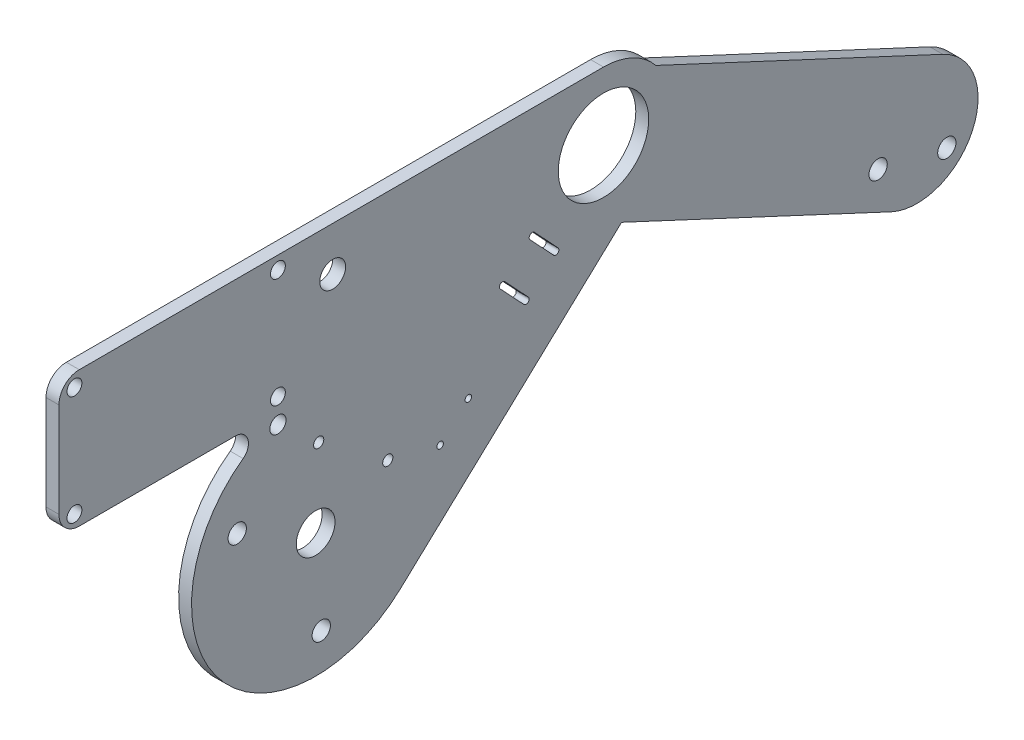
SolidWorks part; units mm, degrees
material "6061 Alloy"
ref_plane "Front Plane" through (0, 0, 0) normal (0, 0, 1) x (1, 0, 0)
ref_plane "Top Plane" through (0, 0, 0) normal (0, 1, 0) x (1, 0, 0)
ref_plane "Right Plane" through (0, 0, 0) normal (1, 0, 0) x (0, 0, -1)
sketch "Sketch1" plane through (0, 0, 0) normal (1, 0, 0) x (0, 0, -1)
  line L0 (-49.9001, -69.4268) -> (11.3662, -12.16)
  line L1 (-133.81, 16.645) -> (-76.19, 16.645)
  line L2 (-133.81, 16.645) -> (-133.81, -16.645)
  line L3 (-133.81, -16.645) -> (-76.19, -16.645)
  line L4 (-76.19, 16.645) -> (-76.19, -16.645)
  line L5 (-130, 13.475) -> (-80, 13.475)
  line L6 (-130, 13.475) -> (-130, -13.475)
  line L7 (-130, -13.475) -> (-80, -13.475)
  line L8 (-80, 13.475) -> (-80, -13.475)
  line L9 (-76.19, 16.645) -> (0, 16.645)
  line L10 (-83.2811, -19.3484) -> (-6.8511, 15.1697)
  line L11 (-130, -13.475) -> (-130, -19.435)
  line L12 (-80, -13.475) -> (-80, -19.435)
  line L13 (-76.19, -16.645) -> (0, -16.645)
  circle A0 centre (0, 0) radius 11.1125
  circle A1 centre (-70.7273, -47.145) radius 4.7625
  circle A2 centre (-70.7273, -47.145) radius 23.015 construction
  circle A3 centre (-70.7273, -47.145) radius 30.5
  circle A4 centre (0, 0) radius 16.645
  circle A5 centre (-130, -19.435) radius 2
  circle A6 centre (-80, -19.435) radius 2
  point P4 (-133.81, 0)
  point P12 (-130, 0)
  dimension "D6" = 22.225
  dimension "D7" = 9.525
  dimension "D8" = 46.03
  dimension "D9" = 61
  dimension "D11" = 0
  dimension "D14" = 4
  dimension "D1" = 33.29
  dimension "D2" = 80
  dimension "D3" = 26.95
  dimension "D4" = 50
  dimension "D5" = 3.81
  dimension "D10" = 85
  dimension "D12" = 3.81
  dimension "D13" = 5.96
extrude "Boss-Extrude1" add sketch "Sketch1" along normal mid plane 3.175 contours A6 A3 A1 | A4 L13 A3 L0 | A4 A0 | A4 L10 L4 L13 | A4 L9 L4 L10 | L8 L12 L3 L10 L4 L1 L2 L11 L6 L5 | L8 L5 L6 L7 | L12 L7 L11 L3 | A6 A3 L13 L3 L10 | L10 L3 L4 | A3 A6 | A3 A6 L10 L12 | L10 A6 A3 L12 | A6 L10 A3 region at (0, -30.4378, 28.398) region at (0, -63.5833, 95.3881) region at (0, -15.0453, -5.9367) region at (0, -18.8843, 82.226) region at (0, -7.4928, 34.7947) region at (0, -18.2558, 80.7031) region at (0, -19.6484, 79.9286) region at (0, -17.0177, 76.5839) region at (0, 5.7227, 51.9516) region at (0, -17.8085, 79.5096) region at (0, -16.4786, 76.5584) region at (0, -15.7889, 77.0165) region at (0, -15.06, 105) region at (0, 0, 105)
sketch "Sketch12" plane through (0, 0, 0) normal (1, 0, 0) x (0, 0, -1)
  line L0 (0, 0) -> (77.0362, -35.9226) construction
  line L1 (6.3393, 13.5946) -> (83.3754, -22.3279)
  line L2 (-6.3393, -13.5946) -> (70.6969, -49.5172)
  line L3 (-1000, 0) -> (49000, 0) construction
  line L5 (-4.9661, -14.2349) -> (77.7852, -34.0471) construction
  arc A0 (6.3393, 13.5946) -> (-6.3393, -13.5946) centre (0, 0) ccw
  arc A1 (70.6969, -49.5172) -> (83.3754, -22.3279) centre (77.0362, -35.9226) ccw
  circle A2 centre (0, 0) radius 11.1125 construction
  circle A3 centre (0, 0) radius 11.1125
  arc A5 (77.7852, -34.0471) -> (91.9205, -34.0633) centre (84.8868, -4.3854) ccw construction
  point P3 (38.5181, -17.9613)
  dimension "D1" = 85
  dimension "D2" = 30
  dimension "D3" = 25
extrude "Boss-Extrude2" add sketch "Sketch12" along normal mid plane 3.175 contours L2 A1 L1 A0 region at (0, -20.3901, -43.7267)
hole_wizard "#6 Clearance Hole1" positions "Sketch2" profile "Sketch3" hole size "#6" standard "ANSI Inch" end condition up to next
sketch "Sketch2" plane through (1.5875, 0, 0) normal (1, 0, 0) x (0, 0, -1)
  point P0 (-80, -13.475)
  point P3 (-80, 13.475)
  point P6 (-130, 13.475)
  point P9 (-130, -13.475)
sketch "Sketch3" plane through (1.5875, -13.475, 80) normal (0, 1, 0) x (0, 0, -1)
  line L0 (0, 0) -> (0, 3.175)
  line L1 (0, 3.175) -> (1.8288, 3.175)
  line L2 (1.8288, 3.175) -> (1.8288, 0)
  line L5 (1.8288, 0) -> (0, 0)
  line L11 (0, -6.35) -> (0, 107.95) construction
  dimension "Thru Hole Dia." = 3.6576
  dimension "Thru Hole Depth" = 3.175
hole_wizard "M3x0.5 Tapped Hole1" positions "Sketch4" profile "Sketch5" tap size "M3x0.5" standard "ANSI Metric" end condition up to next
sketch "Sketch4" plane through (1.5875, 0, 0) normal (1, 0, 0) x (0, 0, -1)
  line L7 (-70.7273, -47.145) -> (-41.414, -6.6391) construction
  line L9 (-69.9837, -28.2416) -> (-53.0036, -40.5297) construction
  point P121 (-61.4936, -34.3856)
  point P124 (-69.9837, -28.2416)
  point P127 (-53.0036, -40.5297)
  dimension "D1" = 20.96
  dimension "D2" = 15.75
  dimension "D3" = 135
  dimension "D4" = 50
sketch "Sketch5" plane through (1.5875, -40.5297, 53.0036) normal (0, 1, 0) x (0, 0, -1)
  line L0 (0, 0) -> (0, 3.175)
  line L1 (0, 3.175) -> (1.25, 3.175)
  line L2 (1.25, 3.175) -> (1.25, 0)
  line L5 (1.25, 0) -> (0, 0)
  line L11 (0, -6.35) -> (0, 107.95) construction
  dimension "Thru Tap Drill Dia." = 2.5
  dimension "Thru Tap Drill Depth" = 3.175
hole_wizard "M4 Clearance Hole1" positions "Sketch6" profile "Sketch7" hole size "M4" standard "ANSI Metric" end condition up to next
sketch "Sketch6" plane through (1.5875, 0, 0) normal (1, 0, 0) x (0, 0, -1)
  line L0 (-70.7273, -47.145) -> (-69.3449, -68.6005) construction
  line L1 (-70.7273, -47.145) -> (-89.9995, -37.6144) construction
  line L3 (-70.7273, -47.145) -> (0, 0) construction
  line L7 (77.0362, -35.9226) -> (84.3628, -42.7285) construction
  line L9 (77.0362, -35.9226) -> (67.4787, -38.8646) construction
  line L10 (77.0362, -35.9226) -> (0, 0) construction
  point P2 (-69.3449, -68.6005)
  point P16 (-89.9995, -37.6144)
  point P37 (67.4787, -38.8646)
  point P40 (84.3628, -42.7285)
  dimension "D1" = 21.5
  dimension "D2" = 120
  dimension "D3" = 120
  dimension "D4" = 120
  dimension "D5" = 10
  dimension "D6" = 17.89
  dimension "D7" = 0
sketch "Sketch7" plane through (1.5875, -42.7285, -84.3628) normal (0, 1, 0) x (0, 0, -1)
  line L0 (0, 0) -> (0, 3.175)
  line L1 (0, 3.175) -> (2.25, 3.175)
  line L2 (2.25, 3.175) -> (2.25, 0)
  line L5 (2.25, 0) -> (0, 0)
  line L11 (0, -6.35) -> (0, 107.95) construction
  dimension "Thru Hole Dia." = 4.5
  dimension "Thru Hole Depth" = 3.175
hole_wizard "M2x0.4 Tapped Hole1" positions "Sketch8" profile "Sketch9" tap size "M2x0.4" standard "ANSI Metric" end condition up to next
sketch "Sketch8" plane through (1.5875, 0, 0) normal (1, 0, 0) x (0, 0, -1)
  line L0 (-49.9001, -69.4268) -> (4.4493, -18.6254) construction
  line L2 (0, 0) -> (34142.961, -36527.4995) construction
  point P0 (-33.212, -37.2653)
  point P2 (-40.1523, -43.7524)
  dimension "D1" = 12.1
  dimension "D2" = 9.5
  dimension "D3" = 12.1
  dimension "D4" = 49.71
sketch "Sketch9" plane through (1.5875, -37.2653, 33.212) normal (0, 1, 0) x (0, 0, -1)
  line L0 (0, 0) -> (0, 3.175)
  line L1 (0, 3.175) -> (0.8, 3.175)
  line L2 (0.8, 3.175) -> (0.8, 0)
  line L5 (0.8, 0) -> (0, 0)
  line L11 (0, -6.35) -> (0, 107.95) construction
  dimension "Thru Tap Drill Dia." = 1.6
  dimension "Thru Tap Drill Depth" = 3.175
cosmetic thread "Hole Thread1" parameters "D2"=2
cosmetic thread "Hole Thread2" parameters "D2"=2
fillet "Fillet1" radius 5 2 edges at (0, -16.645, 133.81) (0, 16.645, 133.81)
fillet "Fillet2" radius 3.175 1 edges at (0, -16.645, 77.2953)
extrude "Cut-Extrude1" cut sketch "Sketch1<3>" against normal through all both and the other way through all contours A3 A6 | A3 A6 L10 L12 | L12 A6 L10 | L10 A6 A3 L12 | L10 A6 L12 region at (0, -17.9759, 80.8435) region at (0, -18.2558, 80.7031) region at (0, -19.6484, 79.9286) region at (0, -17.6074, 79.7609) region at (0, -17.8085, 79.5096)
sketch "Sketch1<3>" plane through (0, 0, 0) normal (1, 0, 0) x (0, 0, -1) same geometry as "Sketch1"
hole_wizard "1/4 (0.2500) Dowel Hole1" positions "Sketch10" profile "Sketch11" hole size "1/4" standard "ANSI Inch" end condition up to next
sketch "Sketch10" plane through (1.5875, 0, 0) normal (1, 0, 0) x (0, 0, -1)
  line L0 (-66.5458, 5.822) -> (0, 0) construction
  line L2 (-1000, 0) -> (49000, 0) construction
  point P0 (-66.5458, 5.822)
  dimension "D1" = 66.8
  dimension "D2" = 5
sketch "Sketch11" plane through (1.5875, 5.822, 66.5458) normal (0, 1, 0) x (0, 0, -1)
  line L0 (0, 0) -> (0, 3.175)
  line L1 (0, 3.175) -> (3.175, 3.175)
  line L2 (3.175, 3.175) -> (3.175, 0)
  line L5 (3.175, 0) -> (0, 0)
  line L11 (0, -6.35) -> (0, 107.95) construction
  dimension "Thru Hole Dia." = 6.35
  dimension "Thru Hole Depth" = 3.175
sketch "Sketch13" plane through (1.5875, 0, 0) normal (1, 0, 0) x (0, 0, -1)
  line L0 (-4.9661, -14.2349) -> (77.7852, -34.0471) construction
  line L1 (-4.9661, -14.2349) -> (77.7852, -34.0471)
  line L2 (-6.3393, -13.5946) -> (70.6969, -49.5172) construction
  line L3 (-4.9661, -14.2349) -> (70.6969, -49.5172)
  arc A0 (77.7852, -34.0471) -> (91.9205, -34.0633) centre (84.8868, -4.3854) ccw construction
  arc A1 (77.7852, -34.0471) -> (91.9205, -34.0633) centre (84.8868, -4.3854) ccw
  arc A2 (70.6969, -49.5172) -> (83.3754, -22.3279) centre (77.0362, -35.9226) ccw construction
  arc A3 (70.6969, -49.5172) -> (91.9205, -34.0633) centre (77.0362, -35.9226) ccw
extrude "Boss-Extrude3" [suppressed] add sketch "Sketch13" along normal blind 10
hole_wizard "Ø1.5mm Dowel Slot1" positions "Sketch14" profile "Sketch15" size "Ø1.5" standard "ANSI Metric" slot yes end condition up to next
sketch "Sketch14" plane through (1.5875, 0, 0) normal (1, 0, 0) x (0, 0, -1)
  line L0 (-18.5022, -24.1385) -> (-25.3308, -16.833) construction
  line L3 (-21.9165, -20.4858) -> (-14.611, -13.6572) construction
  line L6 (-49.9001, -69.4268) -> (4.4493, -18.6254) construction
  point P0 (-21.9165, -20.4858)
  point P4 (-14.611, -13.6572)
  dimension "D1" = 10
  dimension "D2" = 10
  dimension "D3" = 20
sketch "Sketch15" plane through (1.5875, -20.4858, 21.9165) normal (0, 1, 0) x (0, 0, -1)
  line L0 (0, 0) -> (0, 3.175)
  line L1 (0, 3.175) -> (0.75, 3.175)
  line L2 (0.75, 3.175) -> (0.75, 0)
  line L5 (0.75, 0) -> (0, 0)
  line L11 (0, -6.35) -> (0, 107.95) construction
  dimension "Thru Hole Dia." = 1.5
  dimension "Thru Hole Depth" = 3.175
